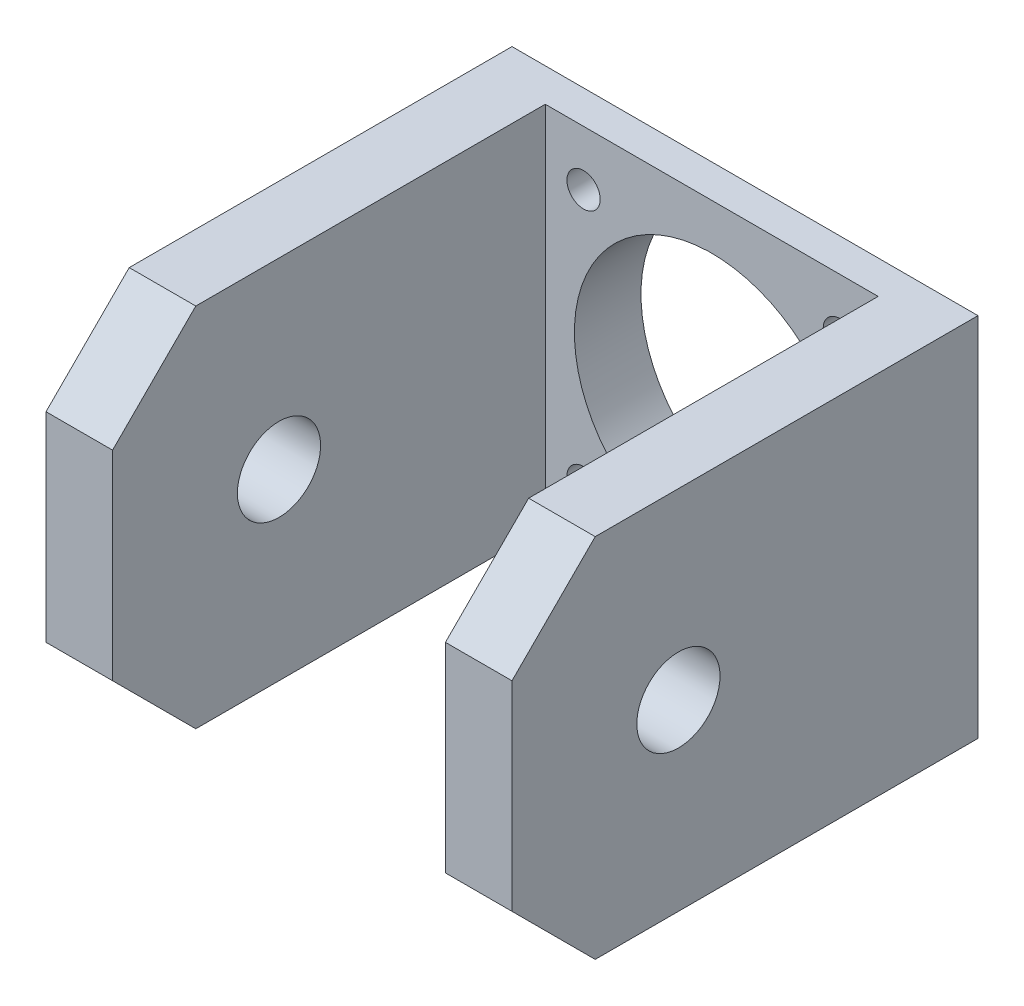
SolidWorks part; units mm, degrees
ref_plane "Front Plane" through (0, 0, 0) normal (0, 0, 1) x (1, 0, 0)
ref_plane "Top Plane" through (0, 0, 0) normal (0, 1, 0) x (1, 0, 0)
ref_plane "Right Plane" through (0, 0, 0) normal (1, 0, 0) x (0, 0, -1)
sketch "Sketch1" plane through (0, 0, 0) normal (1, 0, 0) x (0, 0, -1)
  line L1 (0, 0) -> (30, 0)
  line L2 (0, 0) -> (0, 22)
  line L3 (0, 22) -> (30, 22)
  line L4 (30, 0) -> (30, 22)
  point P7 (30, 0)
  dimension "D1" = 22
  dimension "D2" = 30
extrude "Boss-Extrude1" add sketch "Sketch1" along normal blind 4
sketch "Sketch2" plane through (0, 0, 0) normal (-1, 0, 0) x (0, 0, 1)
  line L0 (0, 0) -> (-30, 0) construction
  line L9 (-30, 22) -> (-26, 22)
  line L10 (-30, 22) -> (-30, 0)
  line L11 (-30, 0) -> (-26, 0)
  line L12 (-26, 22) -> (-26, 0)
  dimension "D1" = 4
extrude "Boss-Extrude2" add sketch "Sketch2" along normal blind 20
sketch "Sketch3" plane through (-20, 0, 0) normal (-1, 0, 0) x (0, 0, 1)
  line L0 (-30, 22) -> (-30, 0)
  line L5 (-30, 0) -> (0, 0)
  line L6 (0, 0) -> (0, 22)
  line L7 (0, 22) -> (-30, 22)
  line L8 (-30, 22) -> (-30, 0) construction
extrude "Boss-Extrude3" add sketch "Sketch3" along normal blind 4
sketch "Sketch4" plane through (4, 0, 0) normal (1, 0, 0) x (0, 0, -1)
  line L0 (0, 22) -> (0, 0) construction
  circle A0 centre (10, 11) radius 2.5
  point P7 (0, 11)
  dimension "D1" = 5
  dimension "D2" = 10
chamfer "Chamfer2" distance 5 angle 45 4 edges at (2, 0, 0) (-22, 0, 0) (2, 22, 0) (-22, 22, 0)
sketch "Sketch8" plane through (0, 0, -26) normal (0, 0, 1) x (1, 0, 0)
  line L0 (-20, 22) -> (0, 22) construction
  line L1 (0, 0) -> (0, 22) construction
  circle A0 centre (-10, 11) radius 8.25
  point P5 (-10, 22)
  point P9 (0, 11)
  dimension "D1" = 16.5
extrude "Cut-Extrude1" cut sketch "Sketch8" against normal up to surface (4 mm away) up to face at (-10, 11, -30)
ref_axis "Axis1" through (-10, 11, -30) along (0, 0, 1)
sketch "Sketch9" plane through (0, 0, -30) normal (0, 0, -1) x (-1, 0, 0)
  line L0 (2.3, 3.3) -> (17.7, 18.7) construction
  circle A0 centre (2.3, 18.7) radius 1
  circle A1 centre (17.7, 18.7) radius 1
  circle A2 centre (17.7, 3.3) radius 1
  circle A3 centre (2.3, 3.3) radius 1
  point P8 (10, 11)
  dimension "D1" = 2
  dimension "D4" = 2
  dimension "D5" = 2
  dimension "D6" = 2
  dimension "D2" = 15.4
  dimension "D3" = 15.4
extrude "Cut-Extrude2" cut sketch "Sketch9" against normal up to surface (4 mm away) up to face at (-1.75, 11, -26)
chamfer "Chamfer3" distance 2 angle 45 4 edges at (-10, 0, -30) (4, 11, -30) (-10, 22, -30) (-24, 11, -30)
extrude "Cut-Extrude3" cut sketch "Sketch4" against normal up to surface (28 mm away) up to face at (-24, 11, -11)
